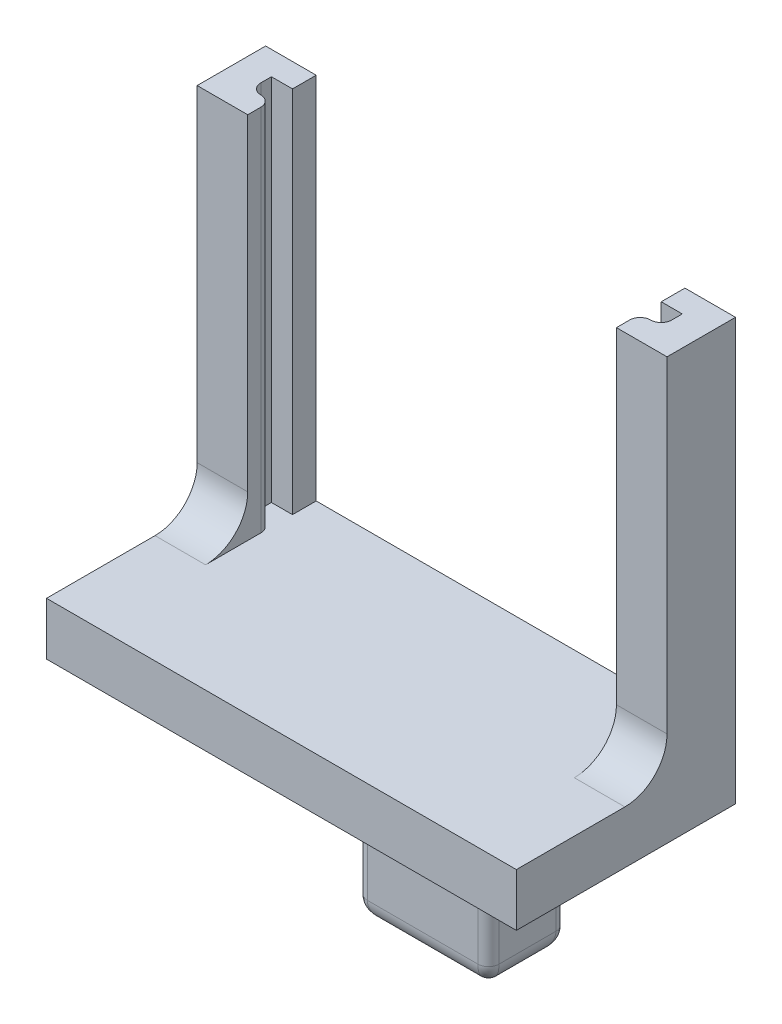
SolidWorks part; units mm, degrees
ref_plane "Front Plane" through (0, 0, 0) normal (0, 0, 1) x (1, 0, 0)
ref_plane "Top Plane" through (0, 0, 0) normal (0, 1, 0) x (1, 0, 0)
ref_plane "Right Plane" through (0, 0, 0) normal (1, 0, 0) x (0, 0, -1)
ref_plane "Plane1" through (0, -19, 0) normal (0, 1, 0) x (1, 0, 0)
sketch "Sketch1" plane through (0, -19, 0) normal (0, 1, 0) x (1, 0, 0)
  line L0 (0, 0) -> (0, -21.3085) construction
  line L1 (-19.5, 0.5) -> (-17.5, 0.5)
  line L2 (-17.5, 0.5) -> (-17.5, 2.75)
  line L3 (-17.5, 2.75) -> (-22.3, 2.75)
  line L4 (-22.3, 2.75) -> (-22.3, -3.75)
  line L5 (-22.3, -3.75) -> (-17.5, -3.75)
  line L6 (-17.5, -3.75) -> (-17.5, -1.5)
  line L7 (-17.5, -1.5) -> (-19.5, -1.5)
  line L8 (-19.5, -1.5) -> (-19.5, 0.5)
  line L10 (19.5, -1.5) -> (19.5, 0.5)
  line L11 (17.5, -1.5) -> (19.5, -1.5)
  line L12 (17.5, -3.75) -> (17.5, -1.5)
  line L13 (22.3, -3.75) -> (17.5, -3.75)
  line L14 (22.3, 2.75) -> (22.3, -3.75)
  line L15 (17.5, 2.75) -> (22.3, 2.75)
  line L16 (17.5, 0.5) -> (17.5, 2.75)
  line L17 (19.5, 0.5) -> (17.5, 0.5)
  dimension "D1" = 2
  dimension "D2" = 17.5
  dimension "D3" = 4.8
  dimension "D4" = 2.25
  dimension "D5" = 0.5
  dimension "D6" = 2
  dimension "D7" = 6.5
extrude "Boss-Extrude1" add sketch "Sketch1" along normal blind 35
sketch "Sketch2" plane through (0, -19, 0) normal (0, 1, 0) x (1, 0, 0)
  line L1 (-22.3, 2.75) -> (22.3, 2.75)
  line L2 (-22.3, 2.75) -> (-22.3, -18.05)
  line L3 (-22.3, -18.05) -> (22.3, -18.05)
  line L4 (22.3, 2.75) -> (22.3, -18.05)
  dimension "D1" = 44.6
  dimension "D2" = 20.8
extrude "Boss-Extrude2" add sketch "Sketch2" against normal blind 5
fillet "Fillet2" radius 4 2 edges at (19.9, -19, 3.75) (-19.9, -19, 3.75)
ref_plane "Plane2" through (0, -24, 0) normal (0, -1, 0) x (-1, 0, 0)
sketch "Sketch4" plane through (0, -24, 0) normal (0, -1, 0) x (-1, 0, 0)
  line L1 (-6.25, 2.75) -> (6.25, 2.75)
  line L2 (-6.25, 2.75) -> (-6.25, -4.65)
  line L3 (-6.25, -4.65) -> (6.25, -4.65)
  line L4 (6.25, 2.75) -> (6.25, -4.65)
  point P6 (-19.8041, 3.8053)
  dimension "D1" = 7.4
  dimension "D2" = 12.5
  dimension "D3" = 6.25
  dimension "D4" = 2.75
extrude "Boss-Extrude4" add sketch "Sketch4" along normal blind 20
fillet "Fillet6" radius 1 4 edges at (-6.25, -34, 4.65) (-6.25, -34, -2.75) (6.25, -34, 4.65) (6.25, -34, -2.75)
fillet "Fillet7" radius 2 8 edges at (5.9571, -44, 4.3571) (6.25, -44, 0.95) (5.9571, -44, -2.4571) (0, -44, -2.75) (-5.9571, -44, -2.4571) (-6.25, -44, 0.95) (-5.9571, -44, 4.3571) (0, -44, 4.65)
fillet "Fillet8" radius 0.5 7 edges at (5.9571, -24, -2.4571) (6.25, -24, 0.95) (5.9571, -24, 4.3571) (-5.9571, -24, -2.4571) (-6.25, -24, 0.95) (-5.9571, -24, 4.3571) (0, -24, 4.65)
fillet "Fillet9" radius 1 4 edges at (-19.5, -1.5, 1.5) (19.5, -1.5, 1.5) (17.5, -1.5, 1.5) (-17.5, -1.5, 1.5)
equation "\"D3@Sketch4\"=\"D2@Sketch4\"/2"
